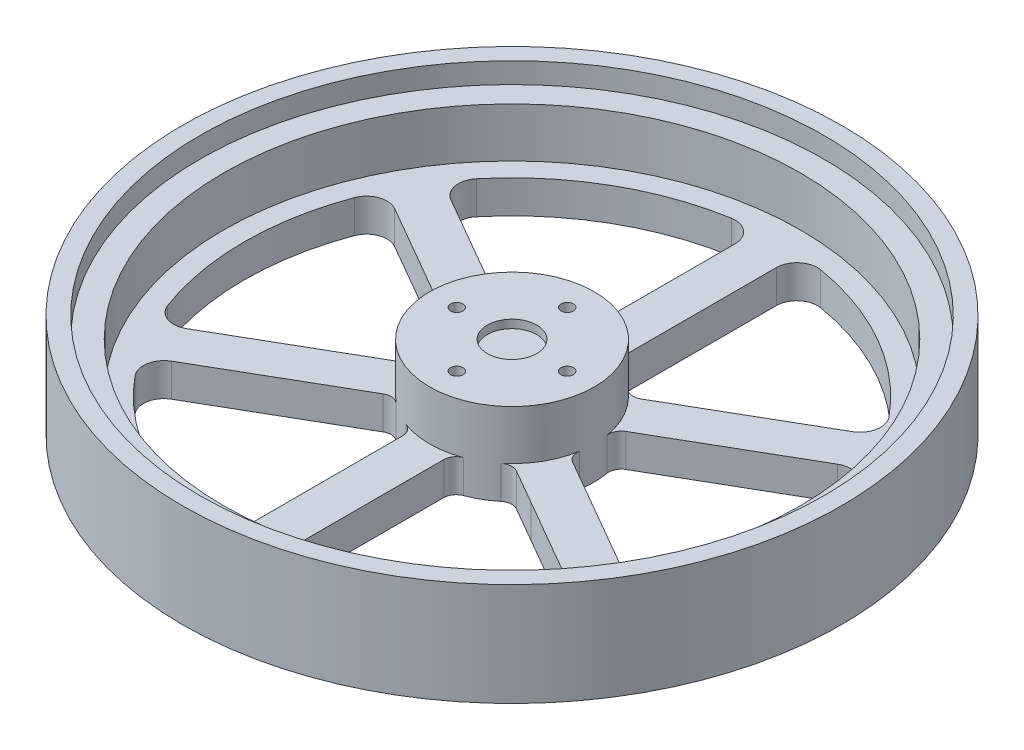
SolidWorks part; units mm, degrees
ref_plane "Front Plane" through (0, 0, 0) normal (0, 0, 1) x (1, 0, 0)
ref_plane "Top Plane" through (0, 0, 0) normal (0, 1, 0) x (1, 0, 0)
ref_plane "Right Plane" through (0, 0, 0) normal (1, 0, 0) x (0, 0, -1)
sketch "Sketch1" plane through (0, 0, 0) normal (0, 1, 0) x (1, 0, 0)
  circle A0 centre (0, 0) radius 75
  dimension "D1" = 150
extrude "Boss-Extrude1" add sketch "Sketch1" along normal blind 8
sketch "Sketch6" plane through (0, 0, 0) normal (0, -1, 0) x (1, 0, 0)
  line L0 (5, -19.3649) -> (23.541, -19.3649)
  line L1 (5, 19.3649) -> (23.541, 19.3649)
  line L3 (5, -64.8074) -> (5, -19.3649)
  line L4 (-5, -64.8074) -> (-5, -19.3649)
  line L5 (-53.6249, -36.7338) -> (-14.2705, -14.0126)
  line L6 (-58.6249, -28.0736) -> (-23.7132, -7.9173)
  line L7 (-58.6249, 28.0736) -> (-23.7132, 7.9173)
  line L8 (-53.6249, 36.7338) -> (-14.2705, 14.0126)
  line L9 (-5, 64.8074) -> (-5, 19.3649)
  line L10 (5, 64.8074) -> (5, 19.3649)
  line L11 (53.6249, 36.7338) -> (23.541, 19.3649)
  line L12 (58.6249, 28.0736) -> (41.2298, 18.0306)
  line L13 (58.6249, -28.0736) -> (41.2298, -18.0306)
  line L14 (53.6249, -36.7338) -> (23.541, -19.3649)
  line L15 (41.2298, 18.0306) -> (58.6249, 28.0736)
  line L16 (-14.2705, -14.0126) -> (-53.6249, -36.7338)
  line L17 (5, 19.3649) -> (5, 64.8074)
  line L18 (5, -19.3649) -> (5, -64.8074)
  line L21 (23.541, -19.3649) -> (53.6249, -36.7338)
  line L22 (-5, -19.3649) -> (-5, -64.8074)
  line L23 (-5, 19.3649) -> (-5, 64.8074)
  line L25 (-23.7132, 7.9173) -> (-58.6249, 28.0736)
  line L26 (-14.2705, 14.0126) -> (-53.6249, 36.7338)
  line L27 (41.2298, -18.0306) -> (58.6249, -28.0736)
  line L28 (-23.7132, -7.9173) -> (-58.6249, -28.0736)
  line L29 (23.541, 19.3649) -> (53.6249, 36.7338)
  arc A1 (58.6249, -28.0736) -> (58.6249, 28.0736) centre (0, 0) ccw
  arc A3 (41.2298, -18.0306) -> (41.2298, 18.0306) centre (0, 0) ccw
  arc A5 (-23.7132, 7.9173) -> (-23.7132, -7.9173) centre (0, 0) ccw
  arc A6 (-5, 19.3649) -> (-14.2705, 14.0126) centre (0, 0) ccw
  arc A10 (5, -64.8074) -> (53.6249, -36.7338) centre (0, 0) ccw
  arc A11 (-53.6249, -36.7338) -> (-5, -64.8074) centre (0, 0) ccw
  arc A12 (-58.6249, 28.0736) -> (-58.6249, -28.0736) centre (0, 0) ccw
  arc A13 (-5, 64.8074) -> (-53.6249, 36.7338) centre (0, 0) ccw
  arc A14 (53.6249, 36.7338) -> (5, 64.8074) centre (0, 0) ccw
  arc A17 (-14.2705, -14.0126) -> (-5, -19.3649) centre (0, 0) ccw
  point P35 (0, 0)
  dimension "D2" = 130
  dimension "D3" = 90
  dimension "D6" = 6
extrude "Cut-Extrude11" cut sketch "Sketch6" against normal through all both and the other way through all contours A3 L13 A1 L12 | L3 A10 L14 L0 | A17 L5 A11 L4 | L7 A12 L6 A5 | L9 A13 L8 A6 | L11 A14 L10 L1 region at (23.37, 0, -40.7131) region at (23.37, 0, 40.7131) region at (-23.1248, 0, -40.0532) region at (-47.3361, 0, 0) region at (-23.1248, 0, 40.0532) region at (54.0019, 0, 0)
fillet "Fillet1" radius 5 24 edges at (53.6249, 4, 36.7338) (5, 4, 64.8074) (-53.6249, 4, 36.7338) (-5, 4, 64.8074) (-58.6249, 4, 28.0736) (-58.6249, 4, -28.0736) (-53.6249, 4, -36.7338) (-5, 4, -64.8074) (5, 4, -64.8074) (53.6249, 4, -36.7338) (58.6249, 4, -28.0736) (58.6249, 4, 28.0736) (41.2298, 4, 18.0306) (41.2298, 4, -18.0306) (5, 4, -19.3649) (23.541, 4, -19.3649) (-14.2705, 4, -14.0126) (-5, 4, -19.3649) (-23.7132, 4, 7.9173) (-23.7132, 4, -7.9173) (-5, 4, 19.3649) (-14.2705, 4, 14.0126) (5, 4, 19.3649) (23.541, 4, 19.3649)
sketch "Sketch7" plane through (0, 8, 0) normal (0, 1, 0) x (1, 0, 0)
  line L0 (-46.1237, -20.856) -> (-19.2705, -5.3523)
  line L1 (-46.1307, 20.8407) -> (-19.2914, 5.2766)
  line L2 (5, -50.3723) -> (5, -19.3649)
  line L3 (46.1237, -20.856) -> (19.2705, -5.3523)
  line L4 (46.1237, 20.856) -> (19.2705, 5.3523)
  line L6 (-5, -50.3723) -> (-5, -19.3649)
  line L7 (-14.2705, -14.0126) -> (-41.1237, -29.5163)
  line L8 (-5, 19.3649) -> (-5, 50.3723)
  line L10 (-14.2705, 14.0126) -> (-41.1237, 29.5163)
  line L11 (5, 19.3649) -> (5, 50.3723)
  line L12 (14.2705, 14.0126) -> (41.1237, 29.5163)
  line L13 (14.2668, -14.0175) -> (41.1237, -29.5178)
  line L14 (41.0935, -29.5584) -> (41.1237, -29.5178)
  line L15 (14.1616, -14.1227) -> (14.2668, -14.0175)
  arc A0 (-14.2705, -14.0126) -> (-5, -19.3649) centre (0, 0) ccw
  arc A2 (5, -19.3649) -> (14.1616, -14.1227) centre (0, 0) ccw
  arc A3 (-19.2914, 5.2766) -> (-19.2705, -5.3523) centre (0, 0) ccw
  arc A4 (-5, 19.3649) -> (-14.2705, 14.0126) centre (0, 0) ccw
  arc A5 (14.2705, 14.0126) -> (5, 19.3649) centre (0, 0) ccw
  arc A6 (5, -50.3723) -> (41.0935, -29.5584) centre (0, 0) ccw
  arc A7 (-41.1237, -29.5163) -> (-5, -50.3723) centre (0, 0) ccw
  arc A8 (-46.1307, 20.8407) -> (-46.1237, -20.856) centre (0, 0) ccw
  arc A9 (-5, 50.3723) -> (-41.1237, 29.5163) centre (0, 0) ccw
  arc A10 (41.1237, 29.5163) -> (5, 50.3723) centre (0, 0) ccw
  arc A11 (46.1237, -20.856) -> (46.1237, 20.856) centre (0, 0) ccw
  arc A12 (19.2705, -5.3523) -> (19.2705, 5.3523) centre (0, 0) ccw
extrude "Cut-Extrude14" cut sketch "Sketch7" against normal through all both and the other way through all
fillet "Fillet2" radius 3 12 edges at (-19.2914, 4, -5.2766) (-19.2705, 4, 5.3523) (-5, 4, -19.3649) (-14.2705, 4, -14.0126) (14.2705, 4, -14.0126) (5, 4, -19.3649) (19.2705, 4, -5.3523) (19.2705, 4, 5.3523) (5, 4, 19.3649) (14.2668, 4, 14.0175) (-5, 4, 19.3649) (-14.2705, 4, 14.0126)
sketch "Sketch8" plane through (0, 8, 0) normal (0, 1, 0) x (1, 0, 0)
  circle A1 centre (-13.4, 0) radius 1.5
  circle A2 centre (0, 13.4) radius 1.5
  circle A3 centre (13.4, 0) radius 1.5
  circle A4 centre (0, -13.4) radius 1.5
  point P5 (0, 0)
  point P6 (0, 0)
  point P14 (0, 0)
  dimension "D2" = 3
  dimension "D3" = 4
extrude "Cut-Extrude15" cut sketch "Sketch8" against normal through all both and the other way through all
sketch "Sketch10" plane through (0, 0, 0) normal (0, -1, 0) x (1, 0, 0)
  circle A0 centre (0, 0) radius 75
  circle A1 centre (0, 0) radius 80
  dimension "D1" = 150
  dimension "D2" = 160
sketch "Sketch18" plane through (0, 8, 0) normal (0, 1, 0) x (1, 0, 0)
  circle A0 centre (0, 0) radius 20
extrude "Boss-Extrude4" add sketch "Sketch18" along normal blind 12
sketch "Sketch19" plane through (0, 0, 0) normal (0, -1, 0) x (1, 0, 0)
  circle A0 centre (13.4, 0) radius 1.5
  circle A1 centre (0, -13.4) radius 1.5
  circle A2 centre (-13.4, 0) radius 1.5
  circle A3 centre (0, 13.4) radius 1.5
extrude "Cut-Extrude23" cut sketch "Sketch19" against normal through all both and the other way through all
sketch "Sketch20" plane through (0, 20, 0) normal (0, 1, 0) x (1, 0, 0)
  circle A0 centre (0, 0) radius 6
  dimension "D1" = 12
extrude "Cut-Extrude25" cut sketch "Sketch20" against normal blind 2
sketch "Sketch21" plane through (0, 0, 0) normal (0, -1, 0) x (1, 0, 0)
  circle A0 centre (13.4, 0) radius 4
  circle A1 centre (0, -13.4) radius 4
  circle A2 centre (0, 13.4) radius 4
  circle A3 centre (-13.4, 0) radius 4
  dimension "D1" = 8
  dimension "D2" = 8
  dimension "D3" = 8
  dimension "D4" = 8
extrude "Cut-Extrude27" cut sketch "Sketch21" against normal blind 10
extrude "Boss-Extrude5" add sketch "Sketch10" against normal blind 25
sketch "Sketch22" plane through (0, 8, 0) normal (0, 1, 0) x (1, 0, 0)
  circle A0 centre (0, 0) radius 75
  circle A1 centre (0, 0) radius 70
  dimension "D1" = 140
extrude "Boss-Extrude7" add sketch "Sketch22" along normal blind 12
sketch "Sketch24" plane through (0, 25, 0) normal (0, 1, 0) x (1, 0, 0)
  circle A0 centre (0, 0) radius 75.75
  dimension "D1" = 151.5
extrude "Cut-Extrude28" cut sketch "Sketch24" against normal blind 5
